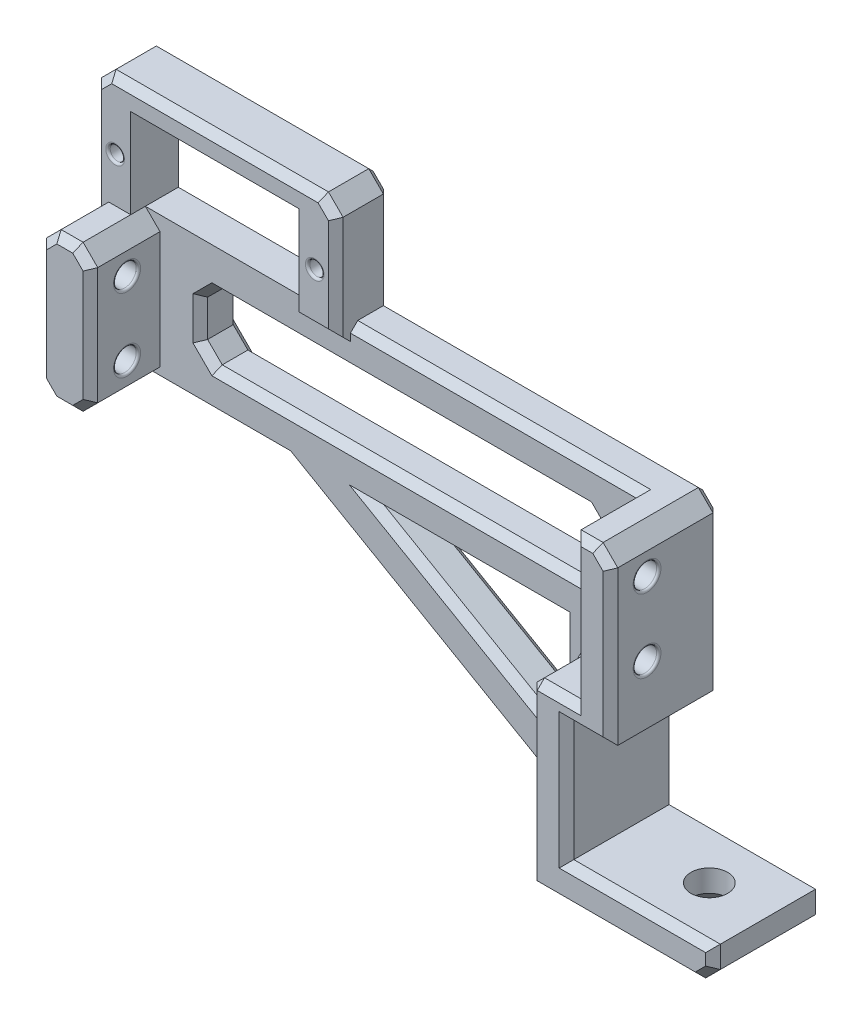
SolidWorks part; units mm, degrees
ref_plane "Plano frontal" through (0, 0, 0) normal (0, 0, 1) x (1, 0, 0)
ref_plane "Plano superior" through (0, 0, 0) normal (0, 1, 0) x (1, 0, 0)
ref_plane "Plano direito" through (0, 0, 0) normal (1, 0, 0) x (0, 0, -1)
sketch "Esboço1" plane through (0, 0, 0) normal (0, 0, 1) x (1, 0, 0)
  line L0 (0, 0) -> (-6, 0)
  line L1 (-6, 0) -> (-6, -16.5)
  line L2 (-6, -16.5) -> (14, -16.5)
  line L3 (14, -16.5) -> (14, -21.5)
  line L4 (14, -21.5) -> (-11, -21.5)
  line L5 (-11, -21.5) -> (-11, 3)
  line L6 (-11, 3) -> (0, 3)
  line L7 (0, 3) -> (0, 0)
  dimension "D1" = 16.5
  dimension "D2" = 6
  dimension "D3" = 20
  dimension "D4" = 5
  dimension "D5" = 3
  dimension "D6" = 5
extrude "Ressalto-extrusão1" add sketch "Esboço1" along normal mid plane 15
ref_plane "Plano3" through (0, 0, -3) normal (0, 0, -1) x (-1, 0, 0)
sketch "Esboço2" plane through (0, 0, -3) normal (0, 0, 1) x (1, 0, 0)
  line L1 (-78, 38.2) -> (-45, 38.2)
  line L2 (-73, 35.2) -> (-73, 23)
  line L3 (-73, 35.2) -> (-50, 35.2)
  line L4 (-50, 35.2) -> (-50, 23)
  line L5 (-73, 23) -> (-50, 23)
  line L6 (-73, 35.2) -> (-50, 23) construction
  line L7 (-50, 35.2) -> (-73, 23) construction
  line L11 (-78, 38.2) -> (-78, 20)
  line L12 (-78, 20) -> (-45, 20)
  line L13 (-45, 38.2) -> (-45, 20)
  line L14 (-11, 3) -> (-11, -21.5) construction
  line L16 (0, 3) -> (-11, 3) construction
  circle A0 centre (-75.125, 29.1) radius 0.975
  circle A1 centre (-47.875, 29.1) radius 0.975
  point P2 (-61.5, 29.1)
  point P13 (-45, 29.1)
  dimension "D3" = 1.95
  dimension "D4" = 1.95
  dimension "D1" = 12.2
  dimension "D2" = 23
  dimension "D5" = 3
  dimension "D6" = 3
  dimension "D7" = 27.25
  dimension "D8" = 13.625
  dimension "D9" = 5
  dimension "D10" = 5
  dimension "D11" = 17
  dimension "D12" = 34
extrude "Ressalto-extrusão2" add sketch "Esboço2" along normal blind 3 separate body
sketch "Esboço3" plane through (0, 0, 0) normal (0, 0, 1) x (1, 0, 0)
  line L0 (-73, 35.2) -> (-73, 23) construction
  line L1 (-75.125, 31.5537) -> (-77.25, 30.3269)
  line L2 (-77.25, 30.3269) -> (-77.25, 27.8731)
  line L3 (-77.25, 27.8731) -> (-75.125, 26.6463)
  line L4 (-75.125, 26.6463) -> (-73, 27.8731)
  line L5 (-73, 27.8731) -> (-73, 30.3269)
  line L6 (-73, 30.3269) -> (-75.125, 31.5537)
  line L7 (-47.875, 31.5537) -> (-50, 30.3269)
  line L8 (-50, 30.3269) -> (-50, 27.8731)
  line L9 (-50, 27.8731) -> (-47.875, 26.6463)
  line L10 (-47.875, 26.6463) -> (-45.75, 27.8731)
  line L11 (-45.75, 27.8731) -> (-45.75, 30.3269)
  line L12 (-45.75, 30.3269) -> (-47.875, 31.5537)
  line L13 (-50, 23) -> (-50, 35.2) construction
  circle A0 centre (-75.125, 29.1) radius 2.125 construction
  circle A1 centre (-47.875, 29.1) radius 2.125 construction
  circle A2 centre (-47.875, 29.1) radius 0.975 construction
  circle A3 centre (-75.125, 29.1) radius 0.975 construction
  circle A4 centre (-47.875, 29.1) radius 0.975
  circle A5 centre (-75.125, 29.1) radius 0.975
  dimension "D1" = 0
  dimension "D2" = 0
extrude "Ressalto-extrusão3" add sketch "Esboço3" against normal blind 6
sketch "Esboço4" plane through (0, 0, -6) normal (0, 0, -1) x (-1, 0, 0)
  line L6 (47.875, 31.5537) -> (45.75, 30.3269)
  line L7 (45.75, 30.3269) -> (45.75, 27.8731)
  line L8 (45.75, 27.8731) -> (47.875, 26.6463)
  line L9 (47.875, 26.6463) -> (50, 27.8731)
  line L10 (50, 27.8731) -> (50, 30.3269)
  line L11 (50, 30.3269) -> (47.875, 31.5537)
  line L12 (47.875, 31.5537) -> (45.75, 30.3269)
  line L13 (45.75, 30.3269) -> (45.75, 27.8731)
  line L14 (45.75, 27.8731) -> (47.875, 26.6463)
  line L15 (47.875, 26.6463) -> (50, 27.8731)
  line L16 (50, 27.8731) -> (50, 30.3269)
  line L17 (50, 30.3269) -> (47.875, 31.5537)
  line L18 (75.125, 31.5537) -> (73, 30.3269)
  line L19 (73, 30.3269) -> (73, 27.8731)
  line L20 (73, 27.8731) -> (75.125, 26.6463)
  line L21 (75.125, 26.6463) -> (77.25, 27.8731)
  line L22 (77.25, 27.8731) -> (77.25, 30.3269)
  line L23 (77.25, 30.3269) -> (75.125, 31.5537)
  line L24 (75.125, 31.5537) -> (73, 30.3269)
  line L25 (73, 30.3269) -> (73, 27.8731)
  line L26 (73, 27.8731) -> (75.125, 26.6463)
  line L27 (75.125, 26.6463) -> (77.25, 27.8731)
  line L28 (77.25, 27.8731) -> (77.25, 30.3269)
  line L29 (77.25, 30.3269) -> (75.125, 31.5537)
  dimension "D1" = 0
  dimension "D2" = 0
extrude "Ressalto-extrusão4" add sketch "Esboço4" along normal blind 1.5
sketch "Esboço6" plane through (0, -21.5, 0) normal (0, -1, 0) x (1, 0, 0)
  line L0 (14, 7.5) -> (14, -7.5) construction
  circle A0 centre (6, 0) radius 2.5
  dimension "D1" = 5
  dimension "D2" = 8
extrude "Corte-extrusão1" cut sketch "Esboço6" against normal blind 9.5
chamfer "Chanfro1" distance 2 angle 45 1 edges at (8.5, -21.5, 0)
ref_plane "Plano1" through (-45.5, 0, 0) normal (-1, 0, 0) x (0, 0, 1)
sketch "Esboço7" plane through (0, 0, 0) normal (1, 0, 0) x (0, 0, -1)
  line L1 (7.5, 3) -> (-7.5, 3)
  line L2 (7.5, 3) -> (7.5, 23)
  line L3 (7.5, 23) -> (-7.5, 23)
  line L4 (-7.5, 3) -> (-7.5, 23)
  circle A1 centre (-2.5, 18) radius 1.6
  circle A2 centre (-2.5, 8) radius 1.6
  dimension "D1" = 3.2
  dimension "D2" = 3.2
  dimension "D3" = 10
  dimension "D4" = 5
  dimension "D5" = 10
  dimension "D6" = 10
  dimension "D7" = 5
  dimension "D8" = 5
extrude "Ressalto-extrusão5" add sketch "Esboço7" against normal blind 5
ref_plane "Plano2" through (-78, 0, 0) normal (1, 0, 0) x (0, 0, -1)
sketch "Esboço9" plane through (-78, 0, 0) normal (1, 0, 0) x (0, 0, -1)
  line L5 (-7.5, 0) -> (-7.5, 23) construction
  line L21 (-7.5, 23) -> (4.5, 23)
  line L22 (-7.5, 23) -> (-7.5, 3)
  line L23 (-7.5, 3) -> (4.5, 3)
  line L25 (4.5, 23) -> (4.5, 3)
  circle A0 centre (-2.5, 8) radius 1.6 construction
  circle A2 centre (-2.5, 18) radius 1.6 construction
  dimension "D2" = 5
  dimension "D3" = 0
  dimension "D1" = 5
extrude "Ressalto-extrusão6" add sketch "Esboço9" along normal blind 2
sketch "Esboço10" plane through (-76, 0, 0) normal (1, 0, 0) x (0, 0, -1)
  line L18 (4.5, 23) -> (4.5, 3)
  line L19 (-7.5, 23) -> (-7.5, 3)
  line L21 (4.5, 23) -> (-7.5, 23)
  line L23 (-7.5, 3) -> (4.5, 3)
  line L24 (4.5, 23) -> (4.5, 3) construction
  circle A0 centre (-2.5, 18) radius 1.6 construction
  circle A2 centre (-2.5, 18) radius 1.6 construction
  circle A4 centre (-2.5, 8) radius 1.6 construction
  circle A5 centre (-2.5, 8) radius 1.6 construction
  circle A6 centre (-2.5, 18) radius 1.55
  circle A7 centre (-2.5, 8) radius 1.55
  dimension "D2" = 0.05
  dimension "D3" = 0.05
  dimension "D1" = 10
  dimension "D4" = 5
  dimension "D5" = 5
  dimension "D6" = 5
  dimension "D8" = 5
extrude "Ressalto-extrusão7" add sketch "Esboço10" along normal blind 5
sketch "Esboço12" plane through (-78, 0, 0) normal (1, 0, 0) x (0, 0, -1)
  line L0 (4.5, 3) -> (7.5, 3)
  line L19 (4.5, 23) -> (4.5, 3)
  line L20 (7.5, 23) -> (7.5, 3)
  line L21 (4.5, 23) -> (7.5, 23)
  line L22 (4.5, 23) -> (3, 23) construction
  line L23 (-7.5, 3) -> (4.5, 3) construction
extrude "Ressalto-extrusão11" add sketch "Esboço12" along normal up to surface (73 mm away) up to face at (-5, 19.6, 2.5)
sketch "Esboço17" plane through (0, 0, 0) normal (0, 0, 1) x (1, 0, 0)
  line L0 (-5, 23) -> (-71, 23) construction
  line L1 (-71, 23) -> (-45, 23)
  line L2 (-71, 23) -> (-71, 20)
  line L3 (-71, 20) -> (-45, 20)
  line L4 (-45, 23) -> (-45, 20)
  line L5 (-71, 23) -> (-71, 3) construction
  line L6 (-71, 20) -> (-45, 20) construction
  line L7 (-45, 20) -> (-45, 38.2) construction
extrude "Corte-extrusão2" cut sketch "Esboço17" against normal up to surface (4.5 mm away) up to face at (-32.6, 11, -4.5)
sketch "Esboço18" plane through (0, 0, -3) normal (0, 0, -1) x (-1, 0, 0)
  line L20 (45, 38.2) -> (45, 23)
  line L21 (45, 23) -> (50, 23)
  line L22 (50, 23) -> (50, 27.8731)
  line L23 (50, 27.8731) -> (47.875, 26.6463)
  line L24 (47.875, 26.6463) -> (45.75, 27.8731)
  line L25 (45.75, 27.8731) -> (45.75, 30.3269)
  line L26 (45.75, 30.3269) -> (47.875, 31.5537)
  line L27 (47.875, 31.5537) -> (50, 30.3269)
  line L28 (50, 30.3269) -> (50, 35.2)
  line L29 (50, 35.2) -> (73, 35.2)
  line L30 (73, 35.2) -> (73, 30.3269)
  line L31 (73, 30.3269) -> (75.125, 31.5537)
  line L32 (75.125, 31.5537) -> (77.25, 30.3269)
  line L33 (77.25, 30.3269) -> (77.25, 27.8731)
  line L34 (77.25, 27.8731) -> (75.125, 26.6463)
  line L35 (75.125, 26.6463) -> (73, 27.8731)
  line L36 (73, 27.8731) -> (73, 23)
  line L37 (73, 23) -> (78, 23)
  line L38 (78, 23) -> (78, 38.2)
  line L39 (78, 38.2) -> (45, 38.2)
  line L40 (45, 38.2) -> (45, 23)
  line L41 (45, 23) -> (50, 23)
  line L42 (50, 23) -> (50, 30.3269)
  line L48 (50, 30.3269) -> (50, 35.2)
  line L49 (50, 35.2) -> (73, 35.2)
  line L50 (73, 35.2) -> (73, 30.3269)
  line L56 (73, 30.3269) -> (73, 23)
  line L58 (78, 23) -> (78, 38.2)
  line L59 (78, 38.2) -> (45, 38.2)
  line L64 (73, 23) -> (78, 23)
  circle A0 centre (75.125, 29.1) radius 0.975 construction
  circle A1 centre (47.875, 29.1) radius 0.975 construction
  circle A2 centre (75.125, 29.1) radius 0.975
  circle A3 centre (47.875, 29.1) radius 0.975
  dimension "D1" = 0
extrude "Ressalto-extrusão14" add sketch "Esboço18" along normal up to surface (4.5 mm away) up to face at (-16.2, -2.4, -7.5)
sketch "Esboço19" plane through (0, 0, -4.5) normal (0, 0, 1) x (1, 0, 0)
  line L0 (-71, 13) -> (-5, 13) construction
  line L1 (-71, 3) -> (-71, 23) construction
  line L2 (-5, 23) -> (-5, 3) construction
  line L3 (-11, 3) -> (-71, 3) construction
  line L4 (-10.5, 8.5) -> (-65.5, 8.5)
  line L5 (-10.5, 8.5) -> (-10.5, 17.5)
  line L6 (-10.5, 17.5) -> (-65.5, 17.5)
  line L7 (-65.5, 8.5) -> (-65.5, 17.5)
  line L8 (-10.5, 8.5) -> (-65.5, 17.5) construction
  line L9 (-10.5, 17.5) -> (-65.5, 8.5) construction
  point P6 (-38, 13)
  dimension "D1" = 5.5
  dimension "D2" = 55
extrude "Corte-extrusão3" cut sketch "Esboço19" against normal blind 10 contours L5 L4 L7 L6
chamfer "Chanfro5" distance 2 angle 45 4 edges at (-65.5, 8.5, -6) (-65.5, 17.5, -6) (-10.5, 8.5, -6) (-10.5, 17.5, -6)
sketch "Esboço20" plane through (0, 0, -7.5) normal (0, 0, -1) x (-1, 0, 0)
  line L0 (11, -21.5) -> (53.4352, 3)
  line L1 (11, 3) -> (11, -21.5) construction
  line L2 (11, -21.5) -> (11, 3)
  line L5 (16, -11.685) -> (41.4352, 3)
  line L8 (16, 3) -> (16, -11.685)
  line L10 (17, -3.7576) -> (27.5524, -5.0153) construction
  line L11 (17, -11.1077) -> (27.5524, -5.0153) construction
  line L12 (17, -11.1077) -> (17, -3.7576) construction
  line L14 (11, 3) -> (46.1741, -1.1922) construction
  line L17 (11, -21.5) -> (46.1741, -1.1922) construction
  line L19 (11, 3) -> (16, 3)
  line L21 (41.4352, 3) -> (53.4352, 3)
  dimension "D1" = 60
  dimension "D3" = 5
  dimension "D2" = 6
extrude "Ressalto-extrusão15" add sketch "Esboço20" against normal blind 3
sketch "Esboço21" plane through (0, 0, -4.5) normal (0, 0, 1) x (1, 0, 0)
  line L0 (-16, -11.685) -> (-16, 3) construction
  line L1 (-41.4352, 3) -> (-16, -11.685) construction
  line L2 (-16, 3) -> (-41.4352, 3) construction
  line L3 (-12.5, 17.5) -> (-10.5, 15.5) construction
  line L4 (-10.5, 10.5) -> (-10.5, 15.5) construction
  line L5 (-10.5, 10.5) -> (-12.5, 8.5) construction
  line L6 (-12.5, 8.5) -> (-63.5, 8.5) construction
  line L7 (-63.5, 8.5) -> (-65.5, 10.5) construction
  line L8 (-65.5, 10.5) -> (-65.5, 15.5) construction
  line L9 (-65.5, 15.5) -> (-63.5, 17.5) construction
  line L10 (-12.5, 17.5) -> (-63.5, 17.5) construction
  line L11 (-16, -11.685) -> (-16, 3)
  line L12 (-5, 23) -> (-45, 23)
  line L16 (-5, 23) -> (-45, 23)
  line L18 (-71, 3) -> (-53.4352, 3)
  line L19 (-53.4352, 3) -> (-11, -21.5)
  line L20 (-11, -21.5) -> (-11, 3)
  line L22 (-11, 3) -> (-5, 3)
  line L23 (-5, 3) -> (-5, 23)
  line L30 (-71, 3) -> (-53.4352, 3)
  line L31 (-53.4352, 3) -> (-11, -21.5)
  line L32 (-11, -21.5) -> (-11, 3)
  line L34 (-11, 3) -> (-5, 3)
  line L35 (-5, 3) -> (-5, 23)
  line L36 (-41.4352, 3) -> (-16, -11.685)
  line L37 (-16, 3) -> (-41.4352, 3)
  line L38 (-12.5, 17.5) -> (-10.5, 15.5)
  line L39 (-10.5, 10.5) -> (-10.5, 15.5)
  line L40 (-10.5, 10.5) -> (-12.5, 8.5)
  line L41 (-12.5, 8.5) -> (-63.5, 8.5)
  line L42 (-63.5, 8.5) -> (-65.5, 10.5)
  line L43 (-65.5, 10.5) -> (-65.5, 15.5)
  line L44 (-65.5, 15.5) -> (-63.5, 17.5)
  line L45 (-12.5, 17.5) -> (-63.5, 17.5)
  line L53 (-45, 23) -> (-50, 23)
  line L54 (-45, 23) -> (-50, 23)
  line L56 (-50, 23) -> (-71, 23)
  line L58 (-50, 23) -> (-71, 23)
  line L60 (-71, 23) -> (-71, 3)
  line L61 (-71, 23) -> (-71, 3)
  dimension "D1" = 0
extrude "Ressalto-extrusão16" add sketch "Esboço21" along normal blind 2.5
chamfer "Chanfro8" distance 2 angle 45 2 edges at (-47.5, 23, -2) (-8, 3, -2)
chamfer "Chanfro9" distance 2 angle 45 8 edges at (14, -21.5, 0) (-71, 23, 2.75) (0, 23, 0) (-78, 3, 0) (-78, 23, 3.75) (-78, 38.2, -3.75) (-45, 38.2, -3.75) (-71, 3, 2.75)
chamfer "Chanfro10" distance 1 angle 45 72 edges at (0.5, -21.5, -7.5) (0, 10.5, -7.5) (-45, 29.6, 0) (-11, -9.25, 7.5) (-61.5, 23, -7.5) (-11, 3, 3.75) (-23.5, 23, -7.5) (-61.5, 35.2, -7.5) (0.5, -21.5, 7.5) (-38, 8.5, -7.5) (-65.5, 13, -7.5) (-38, 17.5, -7.5) (-10.5, 13, -7.5) (-64.5, 9.5, -7.5) (-64.5, 16.5, -7.5) (-11.5, 9.5, -7.5) (-11.5, 16.5, -7.5) (4, -16.5, 7.5) (-28.7176, 3, -7.5) (-64.7176, 3, -7.5) (-32.2176, -9.25, -7.5) (-28.7176, -4.3425, -7.5) (-16, -4.3425, -7.5) (-25, 23, -2) (-63.2176, 3, -2) (-32.2176, -9.25, -2) (-6, -8.25, 7.5) (-28.7176, -4.3425, -2) (-16, -4.3425, -2) (-28.7176, 3, -2) (-38, 17.5, -2) (-64.5, 16.5, -2) (-65.5, 13, -2) (-64.5, 9.5, -2) (-38, 8.5, -2) (-11.5, 9.5, -2) (-10.5, 13, -2) (-11.5, 16.5, -2) (-3, 0, 7.5) (-8, 3, 7.5) (-5, 13, 7.5) (-78, 20.6, -7.5) (-78, 13, 7.5) (-78, 28.6, 0) (-3.5, 23, 7.5) (-61.5, 38.2, -7.5) (-45, 29.6, -7.5) (14, -18, -7.5) (-1, 22, -7.5) (13, -20.5, -7.5) (-77, 4, -7.5) (-46, 37.2, -7.5) (-77, 37.2, -7.5) (-61.5, 38.2, 0) (-46, 37.2, 0) (-77, 37.2, 0) (-71, 13, 7.5) (-74.5, 3, 7.5) (-74.5, 23, 7.5) (-77, 22, 7.5) (-72, 22, 7.5) (-77, 4, 7.5) (-72, 4, 7.5) (14, -18, 7.5) (-1, 22, 7.5) (13, -20.5, 7.5) (0, 10.5, 7.5) (-73, 29.1, -7.5) (-50, 29.1, -7.5) (-3, 0, -7.5) (-6, -8.25, -7.5) (4, -16.5, -7.5)
chamfer "Chanfro11" distance 1 angle 45 1 edges at (-11, -21.5, 1.75)
fillet "Filete1" radius 0.3 8 edges at (0, 9.6, 2.5) (-5, 9.6, 2.5) (0, 19.6, 2.5) (-5, 19.6, 2.5) (-71, 8, 0.95) (-71, 18, 0.95) (-46.9, 29.1, 0) (-74.15, 29.1, 0)
